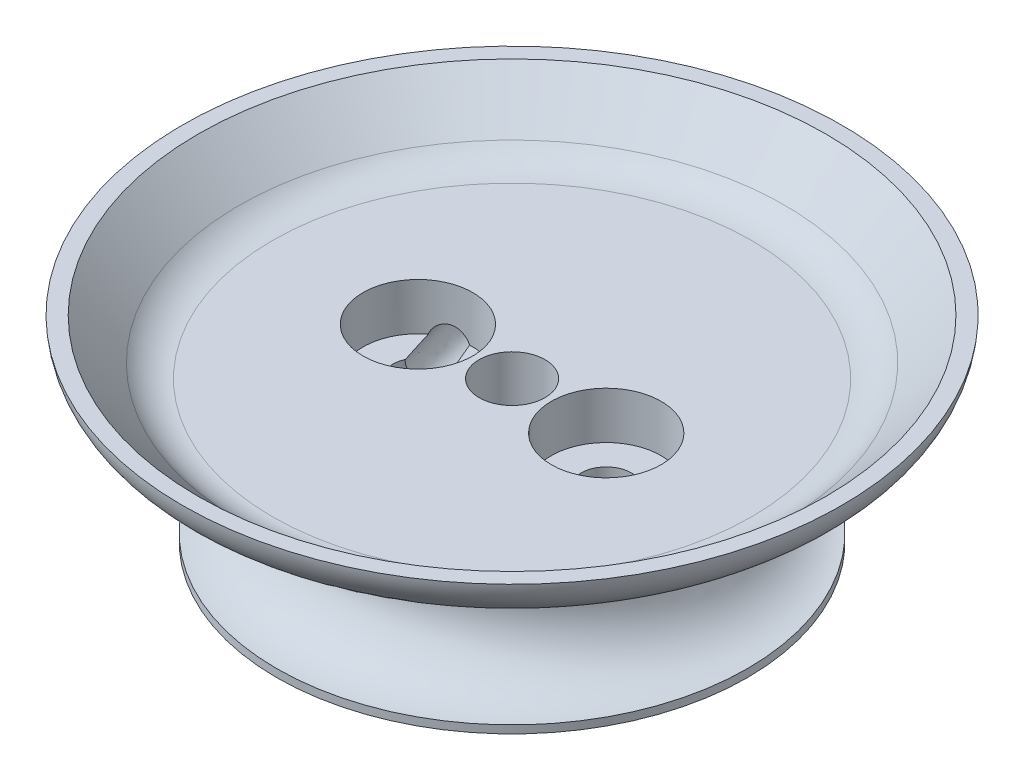
SolidWorks part; units mm, degrees
ref_plane "前视基准面" through (0, 0, 0) normal (0, 0, 1) x (1, 0, 0)
ref_plane "上视基准面" through (0, 0, 0) normal (0, 1, 0) x (1, 0, 0)
ref_plane "右视基准面" through (0, 0, 0) normal (1, 0, 0) x (0, 0, -1)
sketch "草图1" plane through (0, 0, 0) normal (0, 1, 0) x (1, 0, 0)
  circle A0 centre (0, 0) radius 15
  dimension "D1" = 30
extrude "凸台-拉伸1" add sketch "草图1" along normal blind 9
sketch "草图2" plane through (0, 9, 0) normal (0, 1, 0) x (1, 0, 0)
  circle A0 centre (0, 0) radius 2.1
  dimension "D1" = 4.2
extrude "切除-拉伸1" cut sketch "草图2" against normal up to next
sketch "草图3" plane through (0, 9, 0) normal (0, 1, 0) x (1, 0, 0)
  line L0 (-8.4021, 0) -> (9.0244, 0) construction
  line L1 (0, 5.6297) -> (0, -6.9876) construction
  circle A0 centre (-6, 0) radius 1.6
  circle A1 centre (6, 0) radius 1.6
  dimension "D1" = 3.2
  dimension "D2" = 12
extrude "切除-拉伸2" cut sketch "草图3" against normal up to next
sketch "草图4" plane through (0, 9, 0) normal (0, 1, 0) x (1, 0, 0)
  circle A0 centre (-6, 0) radius 3.5
  circle A1 centre (6, 0) radius 3.5
  dimension "D1" = 7
extrude "切除-拉伸3" cut sketch "草图4" against normal blind 3
sketch "草图5" plane through (0, 0, 0) normal (0, 0, 1) x (1, 0, 0)
  line L0 (0, 9) -> (0, 0) construction
  line L1 (2.1, 9) -> (-2.1, 9) construction
  line L2 (0, 4.5) -> (15, 4.5) construction
  line L3 (15, 0) -> (15, 9) construction
  circle A0 centre (15, 4.5) radius 4
  dimension "D1" = 8
revolve "切除-旋转1" cut sketch "草图5" angle 360 about L0
sketch "草图6" plane through (0, 0, 0) normal (0, 0, 1) x (1, 0, 0)
  line L0 (-6, 9) -> (-6, 6) construction
  line L1 (-2.5, 9) -> (-9.5, 9) construction
  line L2 (-2.5, 6) -> (-9.5, 6) construction
  circle A1 centre (-6, 6) radius 1.25
  dimension "D1" = 2.5
ref_plane "基准面1" through (0, 0, -11) normal (0, 0, 1) x (1, 0, 0)
sketch "草图7" plane through (0, 0, -11) normal (0, 0, 1) x (1, 0, 0)
  line L0 (-15, 4.5) -> (-6.0167, 4.5) construction
  line L1 (-15, 8.5) -> (-15, 0.5) construction
  circle A1 centre (-10, 4.5) radius 1.5
  dimension "D1" = 3
  dimension "D2" = 5
sketch "草图8" plane through (0, 0, 0) normal (1, 0, 0) x (0, 0, -1)
  line L0 (0, 14.9257) -> (0, -3.4336) construction
  line L1 (15, 9) -> (15, 12.5)
  line L2 (15, 12.5) -> (21, 12.5)
  line L3 (21, 12.5) -> (21, 11)
  line L5 (15, 8.5) -> (15, 9)
  line L6 (11.0747, 5.2697) -> (21, 11)
  arc A0 (15, 8.5) -> (15, 0.5) centre (15, 4.5) ccw construction
  arc A1 (15, 8.5) -> (11.0747, 5.2697) centre (15, 4.5) ccw
  dimension "D1" = 6
  dimension "D2" = 3.5
  dimension "D3" = 1.5
  dimension "D4" = 30
revolve "旋转1" add sketch "草图8" angle 360 about L0
chamfer "倒角1" distance 5 angle 45 1 edges at (0, 12.5, 15)
fillet "圆角1" radius 3 2 edges at (0, 9, 16.5) (0, 11, 21)
fillet "圆角2" radius 1 1 edges at (0, 5.2697, 11.0747)
loft "切除-放样1" cut profiles "草图6", "草图7" connector at (-7.0823, 6.6255, 0) connector at (-11.314, 3.7765, -11)
